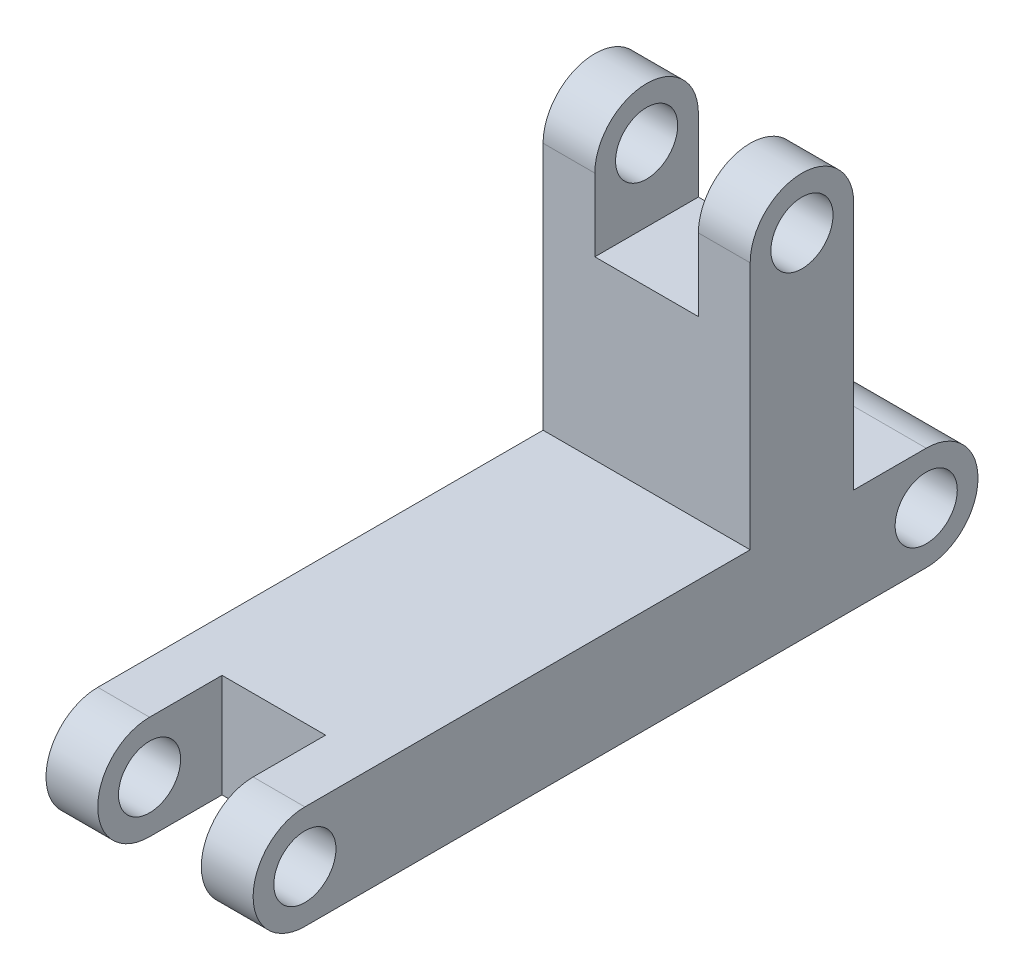
SolidWorks part; units mm, degrees
ref_plane "Alzado" through (0, 0, 0) normal (0, 0, 1) x (1, 0, 0)
ref_plane "Planta" through (0, 0, 0) normal (0, 1, 0) x (1, 0, 0)
ref_plane "Vista lateral" through (0, 0, 0) normal (1, 0, 0) x (0, 0, -1)
sketch "Croquis1" plane through (0, 0, 0) normal (1, 0, 0) x (0, 0, -1)
  line L0 (-15, 0) -> (15, 0) construction
  line L1 (-15, 2.5) -> (6.5, 2.5)
  line L2 (-15, -2.5) -> (15, -2.5)
  line L3 (11.5, 2.5) -> (15, 2.5)
  line L5 (6.5, 2.5) -> (6.5, 14.5)
  line L6 (6.5, 14.5) -> (11.5, 14.5) construction
  line L7 (11.5, 2.5) -> (11.5, 14.5)
  arc A0 (-15, 2.5) -> (-15, -2.5) centre (-15, 0) ccw
  arc A1 (15, -2.5) -> (15, 2.5) centre (15, 0) ccw
  circle A2 centre (15, 0) radius 1.5
  arc A3 (11.5, 14.5) -> (6.5, 14.5) centre (9, 14.5) ccw
  circle A4 centre (9, 14.5) radius 1.5
  circle A5 centre (-15, 0) radius 1.5
  point P3 (0, 0)
  dimension "D2" = 2.5
  dimension "D3" = 3
  dimension "D4" = 2.5
  dimension "D1" = 30
  dimension "D5" = 3.5
  dimension "D6" = 12
extrude "Saliente-Extruir1" add sketch "Croquis1" along normal mid plane 10
sketch "Croquis2" plane through (0, 0, 0) normal (1, 0, 0) x (0, 0, -1)
  line L0 (6.5, 14.5) -> (6.5, 2.5) construction
  line L1 (6.5, 11) -> (11.5, 11)
  line L2 (6.5, 11) -> (6.5, 17)
  line L3 (6.5, 17) -> (11.5, 17)
  line L4 (11.5, 11) -> (11.5, 17)
  line L5 (11.5, 2.5) -> (11.5, 14.5) construction
  line L6 (6.5, 2.5) -> (-15, 2.5) construction
  line L7 (-11.5, 2.5) -> (-17.5, 2.5)
  line L8 (-11.5, 2.5) -> (-11.5, -2.5)
  line L9 (-11.5, -2.5) -> (-17.5, -2.5)
  line L10 (-17.5, 2.5) -> (-17.5, -2.5)
  line L11 (-15, -2.5) -> (15, -2.5) construction
  arc A0 (11.5, 14.5) -> (6.5, 14.5) centre (9, 14.5) ccw construction
  arc A1 (-15, 2.5) -> (-15, -2.5) centre (-15, 0) ccw construction
  dimension "D1" = 6
  dimension "D2" = 6
extrude "Cortar-Extruir1" cut sketch "Croquis2" against normal mid plane 5
